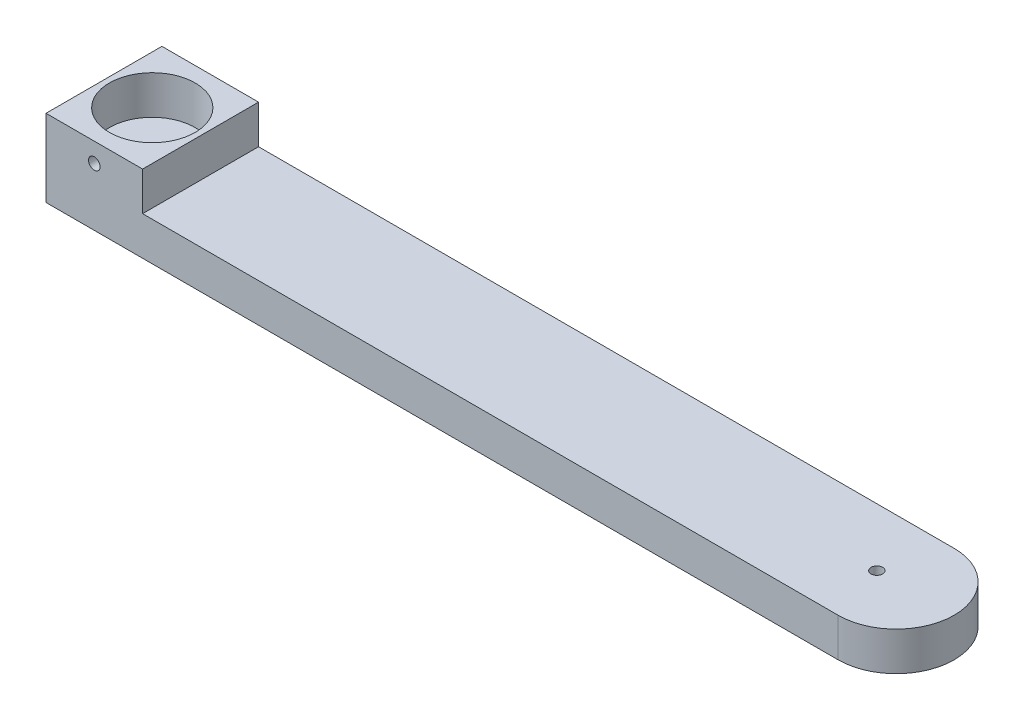
SolidWorks part; units mm, degrees
ref_plane "Front Plane" through (0, 0, 0) normal (0, 0, 1) x (1, 0, 0)
ref_plane "Top Plane" through (0, 0, 0) normal (0, 1, 0) x (1, 0, 0)
ref_plane "Right Plane" through (0, 0, 0) normal (1, 0, 0) x (0, 0, -1)
sketch "Sketch1" plane through (0, 0, 0) normal (0, 1, 0) x (1, 0, 0)
  line L1 (-110, -15) -> (110, -15)
  line L2 (-110, -15) -> (-110, 15)
  line L3 (-110, 15) -> (110, 15)
  line L4 (110, -15) -> (110, 15)
  line L5 (-110, -15) -> (110, 15) construction
  line L6 (-110, 15) -> (110, -15) construction
  circle A0 centre (95, 0) radius 15
  point P0 (0, 0)
  dimension "D3" = 30
  dimension "D1" = 220
  dimension "D2" = 30
extrude "Boss-Extrude1" add sketch "Sketch1" along normal blind 10 contours A0 L3 L2 L1 | A0 region at (-13.3615, 0, 0) region at (95, 0, 0)
sketch "Sketch2" plane through (0, 10, 0) normal (0, 1, 0) x (1, 0, 0)
  line L0 (-5.5, 0) -> (5.5, 0) construction
  line L2 (-85, -15) -> (-110, -15)
  line L3 (-85, -15) -> (-85, 15)
  line L4 (-85, 15) -> (-110, 15)
  line L5 (-110, -15) -> (-110, 15)
  line L6 (-85, -15) -> (-110, 15) construction
  line L7 (-85, 15) -> (-110, -15) construction
  circle A1 centre (-97.5, 0) radius 11.1
  dimension "D1" = 25
  dimension "D2" = 22.2
extrude "Boss-Extrude3" add sketch "Sketch2" along normal blind 10 contours L3 A1 region at (-97.5, 10, 14.6095)
sketch "Sketch4" plane through (0, 10, 0) normal (0, 1, 0) x (1, 0, 0)
  line L0 (-5.5, 0) -> (5.5, 0) construction
  circle A0 centre (90, 0) radius 4
  arc A1 (95, -15) -> (95, 15) centre (95, 0) ccw construction
  dimension "D1" = 8
  dimension "D2" = 5
sketch "Sketch6" plane through (0, 0, 15) normal (0, 0, 1) x (1, 0, 0)
  line L0 (-85, 10) -> (-110, 10) construction
  line L1 (-110, 20) -> (-110, 0) construction
  line L2 (-97.5, 20) -> (-97.5, 10) construction
  circle A0 centre (-97.5, 15) radius 1.5
  dimension "D1" = 3
extrude "Cut-Extrude2" cut sketch "Sketch6" against normal blind 10
extrude "Cut-Extrude3" cut sketch "Sketch4" along normal blind 4 from surface starting at face at (-3.75, 0, 0)
sketch "Sketch7" plane through (0, 4, 0) normal (0, -1, 0) x (-1, 0, 0)
  circle A0 centre (-90, 0) radius 1.5
  dimension "D1" = 3
extrude "Cut-Extrude4" cut sketch "Sketch7" against normal blind 14
